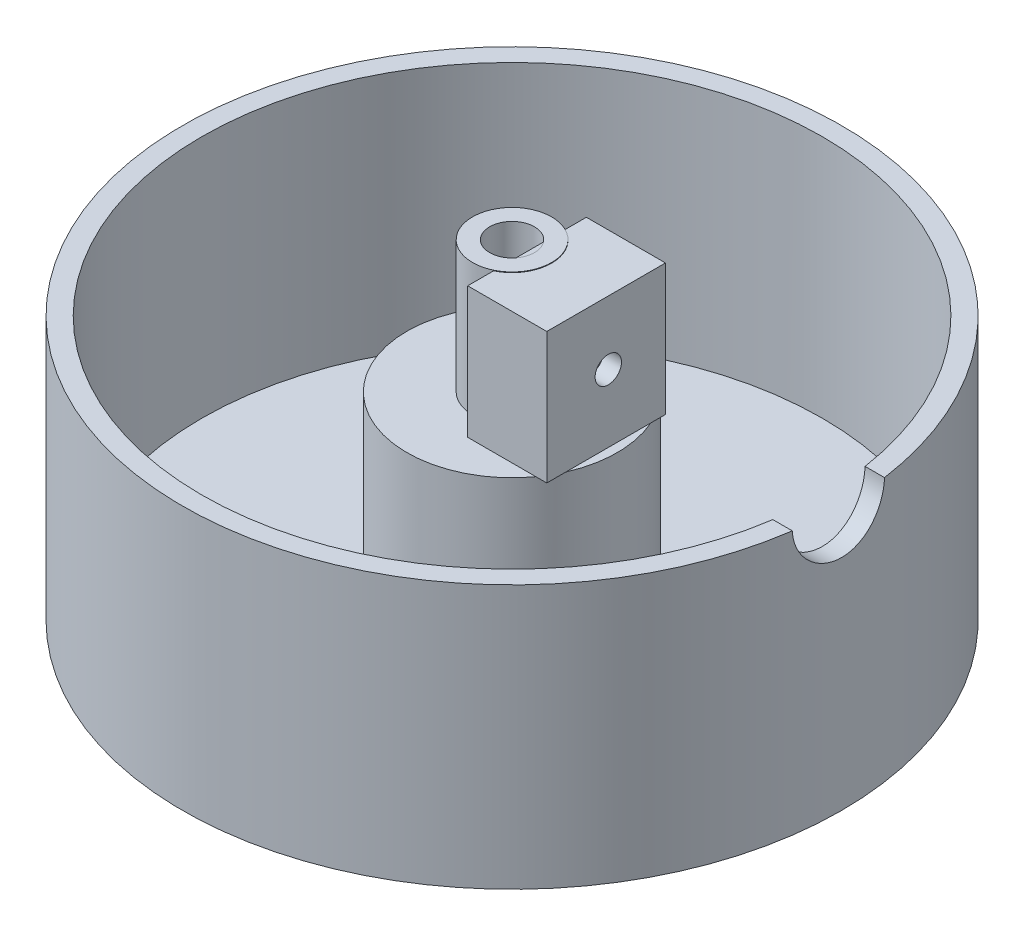
SolidWorks part; units mm, degrees
ref_plane "Front Plane" through (0, 0, 0) normal (0, 0, 1) x (1, 0, 0)
ref_plane "Top Plane" through (0, 0, 0) normal (0, 1, 0) x (1, 0, 0)
ref_plane "Right Plane" through (0, 0, 0) normal (1, 0, 0) x (0, 0, -1)
sketch "Sketch1" plane through (0, 0, 0) normal (0, 1, 0) x (1, 0, 0)
  circle A0 centre (0, 0) radius 6
extrude "Boss-Extrude1" add sketch "Sketch1" along normal blind 20
sketch "Sketch2" plane through (0, 20, 0) normal (0, 1, 0) x (1, 0, 0)
  circle A0 centre (0, 0) radius 3.4
extrude "Cut-Extrude1" cut sketch "Sketch2" against normal blind 13.55 contours A0
ref_plane "Plane1" through (0, 18.26, 0) normal (0, 1, 0) x (1, 0, 0)
ref_axis "Axis1" through (0, 6.45, 0) along (0, 1, 0)
ref_point "Point2"
sketch "Sketch5" plane through (0, 18.26, 0) normal (0, 1, 0) x (1, 0, 0)
  line L0 (0, 0) -> (2.6, 0) construction
  line L2 (2.6, -3.5716) -> (4.1507, -3.5716)
  line L3 (2.6, -3.5716) -> (2.6, 3.6126)
  line L4 (2.6, 3.6126) -> (4.1507, 3.6126)
  line L5 (4.1507, -3.5716) -> (4.1507, 3.6126)
extrude "Boss-Extrude2" add sketch "Sketch5" against normal blind 13.55
sketch "Sketch7" plane through (2.6, 0, 0) normal (-1, 0, 0) x (0, 0, 1)
  line L1 (-8.6717, 19.91) -> (9.3323, 19.91)
  line L2 (-8.6717, 19.91) -> (-8.6717, 0)
  line L3 (-8.6717, 0) -> (9.3323, 0)
  line L4 (9.3323, 19.91) -> (9.3323, 0)
extrude "Boss-Extrude3" add sketch "Sketch7" against normal blind 12
sketch "Sketch6" plane through (2.6, 0, 0) normal (-1, 0, 0) x (0, 0, 1)
  line L1 (-2.1909, 6.45) -> (-2.1909, 19.91) construction
  line L2 (2.1909, 19.91) -> (2.1909, 6.45) construction
  line L3 (-2.1909, 15.4522) -> (2.1909, 15.4522) construction
  circle A0 centre (0, 10.2369) radius 2
extrude "Cut-Extrude2" cut sketch "Sketch6" against normal blind 13.55 and the other way blind 1
ref_axis "Axis2" through (-1.8994, 10.2369, 0) along (-1, 0, 0)
ref_axis "Axis4" through (14.6, 10.2369, 0) along (-1, 0, 0)
ref_plane "Plane3" through (0, 0, 0) normal (0, 0, 1) x (1, 0, 0)
sketch "Sketch9" plane through (0, 0, 0) normal (0, 0, 1) x (1, 0, 0)
  line L0 (11.8765, 10.2369) -> (11.8765, 5.8619)
  line L1 (4.9434, 5.8619) -> (11.8765, 5.8619)
  line L2 (4.9434, 5.8619) -> (4.9434, 10.2369)
  line L3 (4.9434, 10.2369) -> (4.9434, 14.6143)
  line L4 (4.9434, 14.6143) -> (11.8765, 14.6143)
  line L5 (11.8765, 14.6143) -> (11.8765, 10.2369)
  line L6 (14.6, 10.2369) -> (2.6, 10.2369) construction
  line L7 (4.9434, 14.6143) -> (11.8765, 5.8619) construction
extrude "NutOpening" cut sketch "Sketch9" against normal blind 10
sketch "Sketch10" plane through (0, 0, 0) normal (0, -1, 0) x (1, 0, 0)
  circle A0 centre (0, 0) radius 50
extrude "Boss-Extrude4" add sketch "Sketch10" along normal blind 30
sketch "Sketch11" plane through (0, 0, 0) normal (0, 1, 0) x (1, 0, 0)
  line L1 (31.7817, 38.8528) -> (14.4942, 48.0577) construction
  line L2 (14.4942, 48.0577) -> (-5, 49.9462) construction
  line L3 (-5, 49.9462) -> (-23.733, 44.2308) construction
  line L4 (-23.733, 44.2308) -> (-38.8528, 31.7817) construction
  line L5 (-38.8528, 31.7817) -> (-48.0577, 14.4942) construction
  line L6 (-48.0577, 14.4942) -> (-49.9462, -5) construction
  line L7 (-49.9462, -5) -> (-44.2308, -23.733) construction
  line L8 (-44.2308, -23.733) -> (-31.7817, -38.8528) construction
  line L9 (-31.7817, -38.8528) -> (-14.4942, -48.0577) construction
  line L10 (-14.4942, -48.0577) -> (5, -49.9462) construction
  line L11 (5, -49.9462) -> (23.733, -44.2308) construction
  line L12 (23.733, -44.2308) -> (38.8528, -31.7817) construction
  line L13 (38.8528, -31.7817) -> (48.0577, -14.4942) construction
  line L14 (48.0577, -14.4942) -> (49.9462, 5) construction
  line L15 (49.9462, 5) -> (44.2308, 23.733) construction
  line L16 (44.2308, 23.733) -> (31.7817, 38.8528) construction
  circle A0 centre (0, 0) radius 49.2313 construction
  circle A1 centre (5, -49.9462) radius 5
  circle A2 centre (-14.4942, -48.0577) radius 5
  circle A3 centre (-31.7817, -38.8528) radius 5
  circle A4 centre (-44.2308, -23.733) radius 5
  circle A5 centre (-49.9462, -5) radius 5
  circle A6 centre (-48.0577, 14.4942) radius 5
  circle A7 centre (-38.8528, 31.7817) radius 5
  circle A8 centre (-23.733, 44.2308) radius 5
  circle A9 centre (-5, 49.9462) radius 5
  circle A10 centre (14.4942, 48.0577) radius 5
  circle A11 centre (31.7817, 38.8528) radius 5
  circle A12 centre (44.2308, 23.733) radius 5
  circle A13 centre (49.9462, 5) radius 5
  circle A14 centre (48.0577, -14.4942) radius 5
  circle A15 centre (38.8528, -31.7817) radius 5
  circle A16 centre (23.733, -44.2308) radius 5
sketch "Sketch12" plane through (0, 0, 0) normal (0, 1, 0) x (1, 0, 0)
  circle A0 centre (0, 0) radius 47.0828
  circle A1 centre (0, 0) radius 15.9579
extrude "Cut-Extrude5" cut sketch "Sketch12" against normal offset from surface (27 mm away) 3 up to face at (0, -30, -50)
sketch "Sketch13" plane through (0, 0, 0) normal (0, 1, 0) x (1, 0, 0)
  circle A0 centre (0, 0) radius 47.0828
  circle A1 centre (0, 0) radius 50
extrude "Boss-Extrude5" add sketch "Sketch13" along normal blind 10
sketch "Sketch14" plane through (11.8765, 0, 0) normal (-1, 0, 0) x (0, 0, 1)
  line L1 (-5.0541, 10.2369) -> (-2.5271, 5.8599)
  line L2 (-2.5271, 5.8599) -> (2.5271, 5.8599)
  line L3 (2.5271, 5.8599) -> (5.0541, 10.2369)
  line L4 (5.0541, 10.2369) -> (2.5271, 14.6139)
  line L5 (2.5271, 14.6139) -> (-2.5271, 14.6139)
  line L6 (-2.5271, 14.6139) -> (-5.0541, 10.2369)
  circle A0 centre (0, 10.2369) radius 4.377 construction
extrude "Cut-Extrude6" cut sketch "Sketch14" along normal up to surface (6.9331 mm away) up to face at (4.9434, 10.2377, -3.2239)
sketch "Sketch16" plane through (14.6, 0, 0) normal (1, 0, 0) x (0, 0, -1)
  circle A0 centre (0, 10.2369) radius 7
extrude "Cut-Extrude7" cut sketch "Sketch16" along normal blind 40
